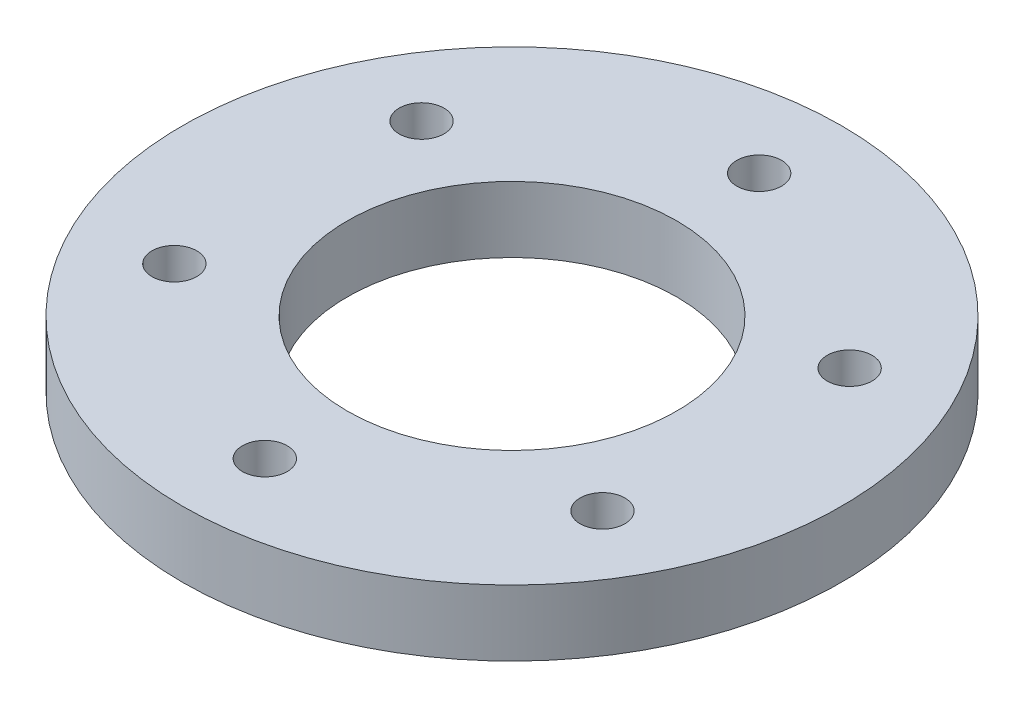
SolidWorks part; units mm, degrees
material "6061-T6 (SS)"
ref_plane "Front Plane" through (0, 0, 0) normal (0, 0, 1) x (1, 0, 0)
ref_plane "Top Plane" through (0, 0, 0) normal (0, 1, 0) x (1, 0, 0)
ref_plane "Right Plane" through (0, 0, 0) normal (1, 0, 0) x (0, 0, -1)
sketch "Sketch1" plane through (0, 0, 0) normal (0, 1, 0) x (1, 0, 0)
  circle A5 centre (16.9825, -21.5042) radius 31.75
  circle A6 centre (16.9825, -21.5042) radius 15.875
  circle A7 centre (-3.6397, -33.4104) radius 2.159
  circle A8 centre (16.9825, -45.3167) radius 2.159
  circle A9 centre (37.6048, -33.4104) radius 2.159
  circle A10 centre (37.6048, -9.5979) radius 2.159
  circle A11 centre (16.9825, 2.3083) radius 2.159
  circle A12 centre (-3.6397, -9.5979) radius 2.159
  dimension "D1" = 63.5
extrude "Boss-Extrude2" add sketch "Sketch1" along normal blind 6.35 contours A5 A12 A11 A10 A9 A8 A7 A6 region at (-13.8694, 0, 21.5042)
